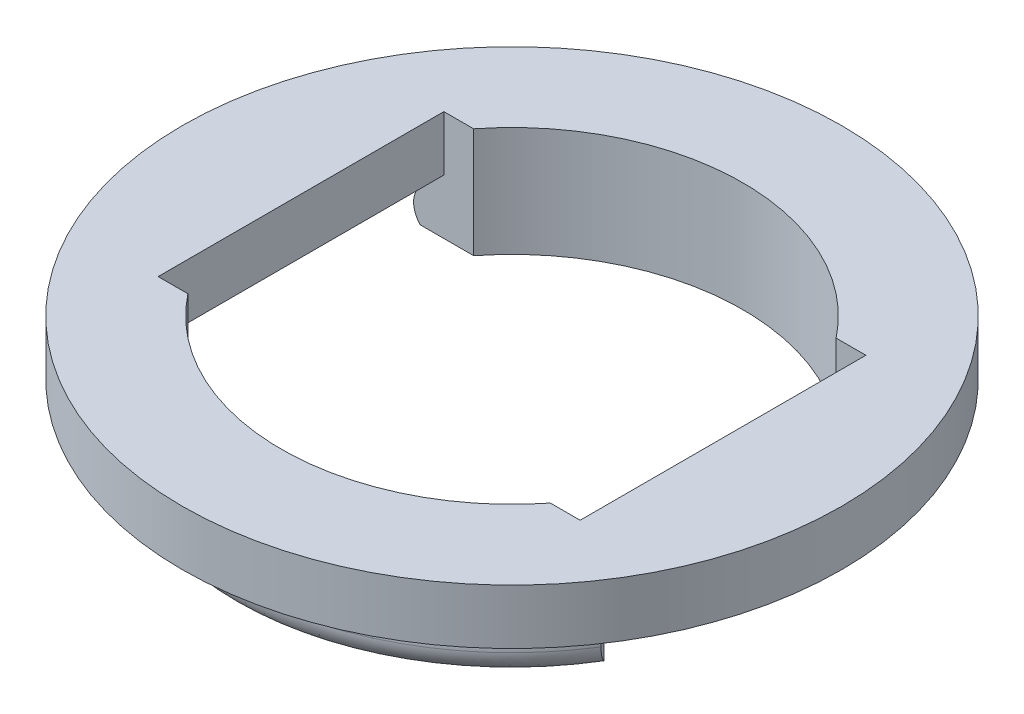
SolidWorks part; units mm, degrees
note: The reader was unsure of these and kept them because the rebuilt part matched: shared geometry of "Sketch2<3>".
ref_plane "Front Plane" through (0, 0, 0) normal (0, 0, 1) x (1, 0, 0)
ref_plane "Top Plane" through (0, 0, 0) normal (0, 1, 0) x (1, 0, 0)
ref_plane "Right Plane" through (0, 0, 0) normal (1, 0, 0) x (0, 0, -1)
sketch "Sketch1" plane through (0, 0, 0) normal (0, 1, 0) x (1, 0, 0)
  line L0 (0, 15) -> (0, 0) construction
  line L1 (-9.6, 6.5) -> (9.6, 6.5)
  line L2 (-9.6, 6.5) -> (-9.6, -6.5)
  line L3 (-9.6, -6.5) -> (9.6, -6.5)
  line L4 (9.6, 6.5) -> (9.6, -6.5)
  line L5 (0, 0) -> (0, -15) construction
  line L6 (9.6, 6.5) -> (0, 0) construction
  line L7 (15, 0) -> (0, 0) construction
  line L8 (0, 0) -> (-15, 0) construction
  line L9 (0, 0) -> (-9.6, -6.5) construction
  line L10 (-9.6, 6.5) -> (0, 0) construction
  line L11 (0, 0) -> (9.6, -6.5) construction
  line L12 (-9.6, 6.5) -> (-13.5185, 6.5)
  line L13 (9.6, 6.5) -> (13.5185, 6.5)
  line L14 (9.6, -6.5) -> (13.5185, -6.5)
  line L15 (-9.6, -6.5) -> (-13.5185, -6.5)
  circle A0 centre (0, 0) radius 15
  dimension "D1" = 30
  dimension "D2" = 19.2
  dimension "D3" = 13
extrude "Boss-Extrude1" add sketch "Sketch1" along normal blind 2.5 contours L12 A0 L15 L2 | L15 A0 L14 L3 | L13 A0 L12 L1 | L14 A0 L13 L4
sketch "Sketch2" plane through (0, 0, 0) normal (0, -1, 0) x (1, 0, 0)
  line L0 (-21.7909, 6.5) -> (22.0222, 6.5)
  line L1 (21.3282, -6.5) -> (-23.4564, -6.5)
  circle A0 centre (0, 0) radius 12.5
  circle A1 centre (0, 0) radius 10.5
  line M6 (-9.6, 6.5) -> (9.6, 6.5)
  line M8 (9.6, -6.5) -> (-9.6, -6.5)
  dimension "D1" = 25
  dimension "D2" = 21
  dimension "D3" = 13
extrude "Boss-Extrude2" add sketch "Sketch2" along normal blind 2.5 contours A1 L0 A0 M6 | A1 L1 A0 M8
extrude "Cut-Extrude1" cut sketch "Sketch2<3>" against normal through all both and the other way through all contours L0 A1 | L1 A1
sketch "Sketch2<3>" plane through (0, 0, 0) normal (0, -1, 0) x (1, 0, 0) same geometry as "Sketch2"
sketch "Sketch4" plane through (0, 0, 6.5) normal (0, 0, -1) x (-1, 0, 0)
  line L0 (10.6771, -2.5) -> (10.6771, -1) construction
  line L1 (10.6771, -2.5) -> (10.6771, 0) construction
  line L2 (10.6771, -1.75) -> (10.9771, -1.75) construction
  line L3 (10.6771, -2.5) -> (10.6771, -1)
  line L4 (10.6771, -2.5) -> (10.6771, -1)
  arc A0 (10.9771, -1.75) -> (10.6771, -2.5) centre (9.8896, -1.75) cw
  arc A1 (10.9771, -1.75) -> (10.6771, -1) centre (9.8896, -1.75) ccw
  dimension "D1" = 1.5
  dimension "D2" = 0.3
sweep "Sweep2" add profiles "Sketch4" path edge at (0, -2.5, 12.5)
sketch "Sketch11" plane through (0, 0, -6.5) normal (0, 0, 1) x (1, 0, 0)
  line L0 (-10.6771, -2.5) -> (-10.6771, -1)
  line L1 (-10.6771, -2.5) -> (-10.6771, 0) construction
  line L2 (-10.6771, -1.75) -> (-10.9771, -1.75) construction
  line L3 (-10.6771, -2.5) -> (-10.6771, -1)
  arc A1 (-10.9771, -1.75) -> (-10.6771, -2.5) centre (-9.8896, -1.75) ccw
  arc A2 (-10.9771, -1.75) -> (-10.6771, -1) centre (-9.8896, -1.75) cw
  dimension "D1" = 1.5
  dimension "D2" = 0.3
sweep "Sweep4" add profiles "Sketch11" path edge at (0, -2.5, -12.5)
